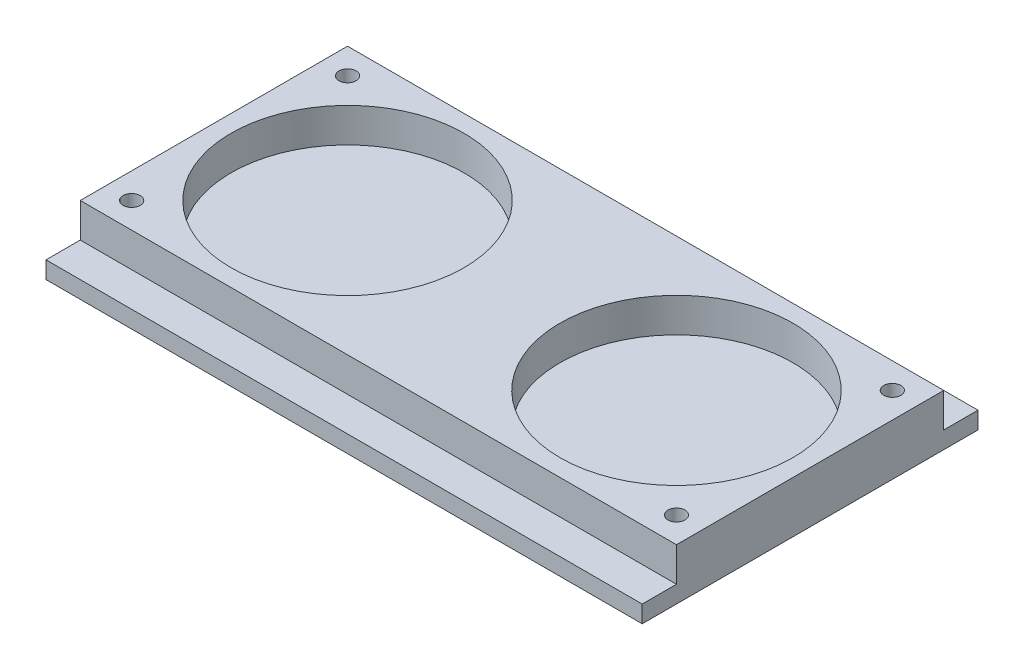
SolidWorks part; units mm, degrees
ref_plane "Front Plane" through (0, 0, 0) normal (0, 0, 1) x (1, 0, 0)
ref_plane "Top Plane" through (0, 0, 0) normal (0, 1, 0) x (1, 0, 0)
ref_plane "Right Plane" through (0, 0, 0) normal (1, 0, 0) x (0, 0, -1)
sketch "Sketch1" plane through (0, 0, 0) normal (0, 1, 0) x (1, 0, 0)
  line L0 (0, 0) -> (48, 0) construction
  line L1 (0, 0) -> (-48, 0) construction
  line L2 (48, 0) -> (48, 34) construction
  line L3 (48, 34) -> (48, 39) construction
  line L4 (48, 0) -> (82, 0) construction
  line L5 (82, 0) -> (87, 0) construction
  line L6 (-48, 0) -> (-82, 0) construction
  line L7 (-82, 0) -> (-87, 0) construction
  line L8 (-48, 0) -> (-48, -34) construction
  line L9 (-48, -34) -> (-48, -39) construction
  line L10 (-87, -39) -> (-87, -49)
  line L11 (-87, -39) -> (87, -39)
  line L12 (-87, -39) -> (-87, 39)
  line L13 (-87, 39) -> (87, 39)
  line L14 (87, -39) -> (87, 39)
  line L15 (-87, -49) -> (87, -49)
  line L16 (87, -49) -> (87, -39)
  line L17 (87, 39) -> (87, 49)
  line L18 (87, 49) -> (-87, 49)
  line L19 (-87, 49) -> (-87, 39)
  line L20 (-78.1459, 39) -> (-78.1459, 31.5) construction
  line L21 (-87, 31.5) -> (-79.5, 31.5) construction
  line L22 (-79.5, -39) -> (-79.5, -31.5) construction
  line L23 (87, -31.5) -> (79.5, -31.5) construction
  line L24 (79.5, 39) -> (79.5, 31.5) construction
  circle A0 centre (48, 0) radius 34
  circle A1 centre (-48, 0) radius 34
  circle A2 centre (-79.5, 31.5) radius 2.5
  circle A3 centre (-79.5, -31.5) radius 2.5
  circle A4 centre (79.5, -31.5) radius 2.5
  circle A5 centre (79.5, 31.5) radius 2.5
extrude "Boss-Extrude1" add sketch "Sketch1" along normal blind 10 contours L11 L14 L13 L12 A5 A4 A3 A2 A1 A0 region at (0, 0, 0)
extrude "Boss-Extrude2" add sketch "Sketch1<3>" against normal blind 5 contours A0 | L11 L14 L13 L12 A5 A4 A3 A2 A1 A0 | L15 L16 L11 L10 | L18 L19 L13 L17 | A1 region at (0, 0, 44) region at (0, 0, 0) region at (0, 0, -44) region at (48, 0, 0) region at (-48, 0, 0)
sketch "Sketch1<3>" plane through (0, 0, 0) normal (0, 1, 0) x (1, 0, 0) same geometry as "Sketch1"
